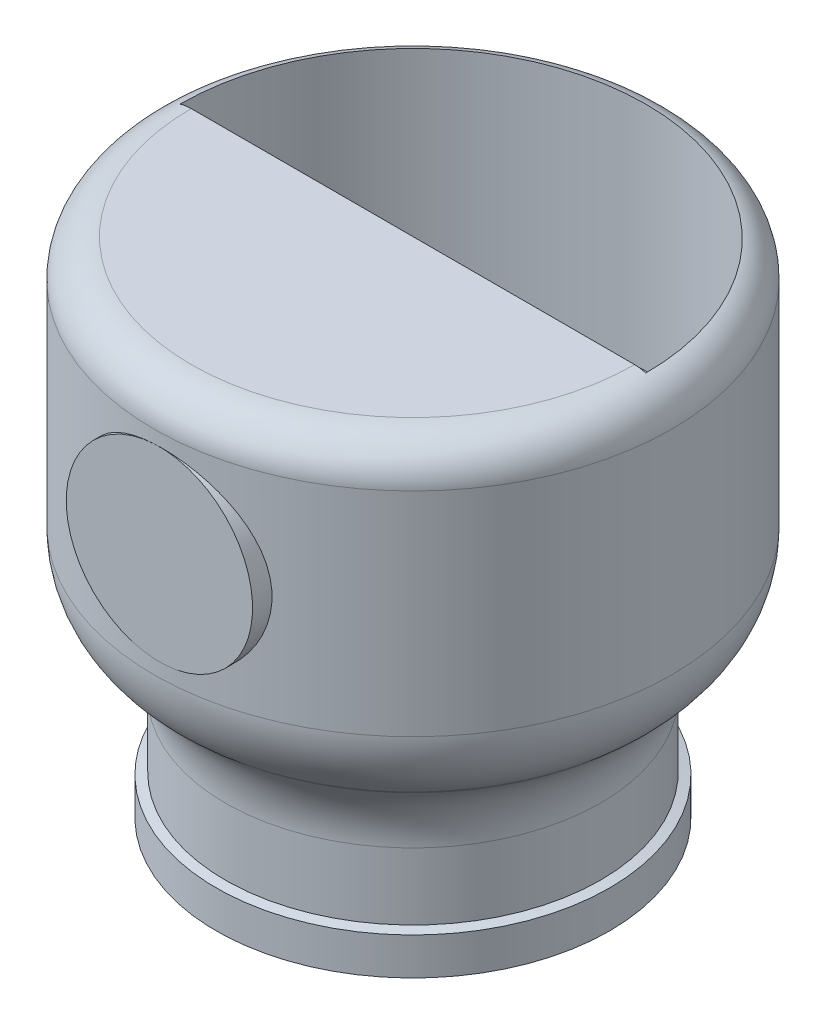
SolidWorks part; units mm, degrees
ref_plane "Front Plane" through (0, 0, 0) normal (0, 0, 1) x (1, 0, 0)
ref_plane "Top Plane" through (0, 0, 0) normal (0, 1, 0) x (1, 0, 0)
ref_plane "Right Plane" through (0, 0, 0) normal (1, 0, 0) x (0, 0, -1)
sketch "Sketch1" plane through (0, 0, 0) normal (0, 0, 1) x (1, 0, 0)
  line L0 (2.7649, 7.8218) -> (2.7649, 58.3592) construction
  line L1 (20.9, 0) -> (23.8716, 0)
  line L2 (23.8716, 0) -> (23.8716, 4)
  line L3 (23.8716, 4) -> (22.9, 4.2367)
  line L4 (22.9, 4.2367) -> (22.9, 11.4043)
  line L6 (20.9, 0) -> (20.9, 14)
  line L12 (19.9, 15) -> (2.7649, 15)
  line L17 (26.4721, 19.0648) -> (26.9883, 19.4979)
  line L18 (30.5604, 27.1583) -> (30.5604, 50)
  line L20 (26.5604, 54) -> (2.7649, 54)
  line L22 (2.7649, 15) -> (2.7649, 54)
  arc A1 (30.5604, 50) -> (26.5604, 54) centre (26.5604, 50) ccw
  arc A2 (26.4721, 19.0648) -> (22.9, 11.4043) centre (32.9, 11.4043) ccw
  arc A3 (26.9883, 19.4979) -> (30.5604, 27.1583) centre (20.5604, 27.1583) ccw
  arc A6 (20.9, 14) -> (19.9, 15) centre (19.9, 14) ccw
  point P11 (22.9, 54)
  point P28 (28.5604, 23.4279)
  point P31 (20.9, 17)
  dimension "D9" = 4
  dimension "D16" = 10
  dimension "D19" = 1
  dimension "D2" = 4
  dimension "D3" = 1
  dimension "D6" = 2
  dimension "D7" = 2.9716
  dimension "D11" = 15
  dimension "D15" = 10
revolve "Revolve1" add sketch "Sketch1" angle 360 about L0
ref_plane "Plane1" through (0, 4, 0) normal (0, 1, 0) x (1, 0, 0)
sketch "Sketch3" plane through (0, 0, 0) normal (0, 0, 1) x (1, 0, 0)
  point P0 (1.2404, 19.1989)
ref_point "Point1"
ref_plane "Plane2" through (0, 0, 22.9) normal (0, 0, 1) x (1, 0, 0)
ref_plane "Plane3" through (0, 0, 27.7955) normal (0, 0, 1) x (1, 0, 0)
ref_plane "Plane4" through (0, 54, 0) normal (0, 1, 0) x (1, 0, 0)
sketch "Sketch9" plane through (0, 54, 0) normal (0, 1, 0) x (1, 0, 0)
  line L0 (-22.2351, 0) -> (27.7649, 0)
  arc A0 (27.7649, 0) -> (-22.2351, 0) centre (2.7649, 0) ccw
  circle A3 centre (2.7649, 0) radius 23.7955 construction
  point P1 (0, 0)
  dimension "D1" = 50
  dimension "D3" = 25
  dimension "D4" = 0
extrude "Cut-Extrude2" cut sketch "Sketch9" against normal blind 25
sketch "Sketch10" plane through (0, 0, 27.7955) normal (0, 0, 1) x (1, 0, 0)
  line L0 (30.5604, 27.1583) -> (-25.0306, 27.1583) construction
  circle A0 centre (3.3463, 38.6583) radius 10
  dimension "D1" = 20
  dimension "D2" = 11.5
extrude "Boss-Extrude1" add sketch "Sketch10" against normal blind 5
ref_plane "Plane5" through (0, 17, 0) normal (0, 1, 0) x (1, 0, 0)
sketch "Sketch11" plane through (0, 17, 0) normal (0, 1, 0) x (1, 0, 0)
  line L0 (-14.7351, 0) -> (20.2649, 0)
  arc A1 (-14.7351, 0) -> (20.2649, 0) centre (2.7649, 0) cw
  circle A2 centre (2.7649, 0) radius 20.9233 construction
  point P6 (0, 0)
  point P7 (0, 0)
  point P8 (0, 0)
  point P9 (0, 0)
  point P10 (0, 0)
  dimension "D2" = 0
  dimension "D1" = 35
extrude "Cut-Extrude3" cut sketch "Sketch11" against normal blind 10 and the other way blind 15
